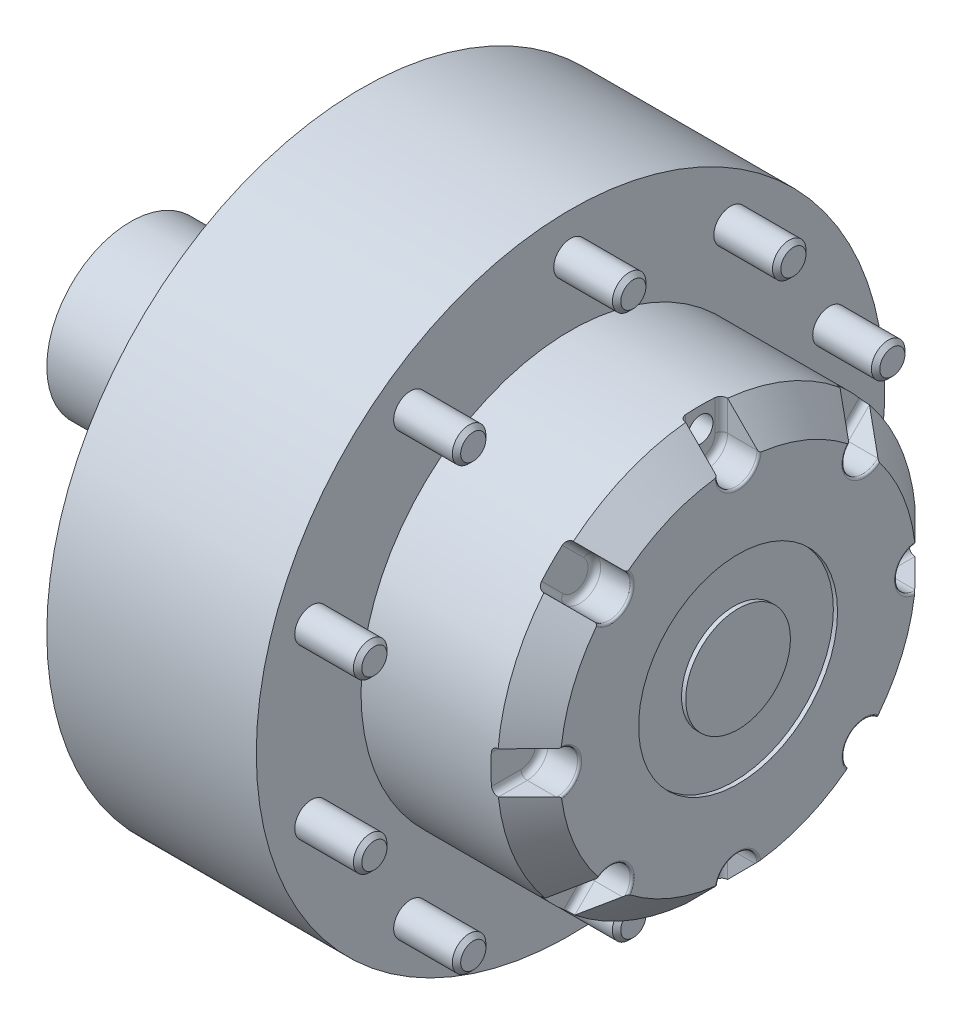
SolidWorks part; units mm, degrees
ref_plane "Front Plane" through (0, 0, 0) normal (0, 0, 1) x (1, 0, 0)
ref_plane "Top Plane" through (0, 0, 0) normal (0, 1, 0) x (1, 0, 0)
ref_plane "Right Plane" through (0, 0, 0) normal (1, 0, 0) x (0, 0, -1)
sketch "Sketch1" plane through (0, 0, 0) normal (0, 0, 1) x (1, 0, 0)
  line L0 (0, 150) -> (0, 0)
  line L1 (0, 0) -> (180, 0)
  line L2 (180, 0) -> (180, 85)
  line L3 (165, 100) -> (100, 100)
  line L4 (100, 100) -> (100, 150)
  line L5 (100, 150) -> (0, 150)
  line L6 (180, 85) -> (165, 100)
  point P5 (180, 100)
  dimension "D1" = 180
  dimension "D2" = 100
  dimension "D3" = 80
  dimension "D4" = 50
revolve "Revolve1" add sketch "Sketch1" angle 360 about L1
sketch "Sketch2" plane through (0, 0, 0) normal (-1, 0, 0) x (0, 0, 1)
  circle A0 centre (0, 0) radius 40
  dimension "D1" = 80
extrude "Boss-Extrude1" add sketch "Sketch2" along normal blind 110
sketch "Sketch3" plane through (180, 0, 0) normal (1, 0, 0) x (0, 0, -1)
  line L2 (-10, 85) -> (-10, 110)
  line L3 (-10, 110) -> (10, 110)
  line L4 (10, 85) -> (10, 110)
  arc A0 (-10, 85) -> (10, 85) centre (0, 85) ccw
  point P6 (0, 0)
  point P8 (0, 0)
  dimension "D2" = 20
  dimension "D1" = 85
  dimension "D3" = 25
extrude "Cut-Extrude1" cut sketch "Sketch3" against normal blind 18
fillet "Fillet1" radius 3 3 edges at (162, 92.2494, -10) (162, 75, 0) (162, 92.2494, 10)
fillet "Fillet2" radius 1 1 edges at (180, 75, 0)
pattern_circular "CirPattern1" count 8 over 360 about axis through (0, -0.6585, 0) along (1, 0, 0) of "Fillet2", "Cut-Extrude1", "Fillet1"
sketch "Sketch4" plane through (100, 0, 0) normal (1, 0, 0) x (0, 0, -1)
  circle A0 centre (0, 130) radius 8
  dimension "D2" = 16
  dimension "D1" = 130
extrude "Boss-Extrude2" add sketch "Sketch4" along normal blind 30
chamfer "Chamfer1" distance 2 angle 45 1 edges at (130, 130, -8)
pattern_circular "CirPattern2" count 10 over 360 about axis through (0, 0, 0) along (1, 0, 0) of "Chamfer1", "Boss-Extrude2"
sketch "Sketch5" plane through (180, 0, 0) normal (1, 0, 0) x (0, 0, -1)
  circle A0 centre (0, 90) radius 6
  dimension "D2" = 12
  dimension "D1" = 90
extrude "Cut-Extrude2" cut sketch "Sketch5" against normal blind 35
sketch "Sketch6" plane through (180, 0, 0) normal (1, 0, 0) x (0, 0, -1)
  circle A0 centre (0, 0) radius 47.5
  circle A1 centre (0, 0) radius 25
  dimension "D1" = 95
  dimension "D2" = 50
extrude "Cut-Extrude3" cut sketch "Sketch6" against normal blind 2
